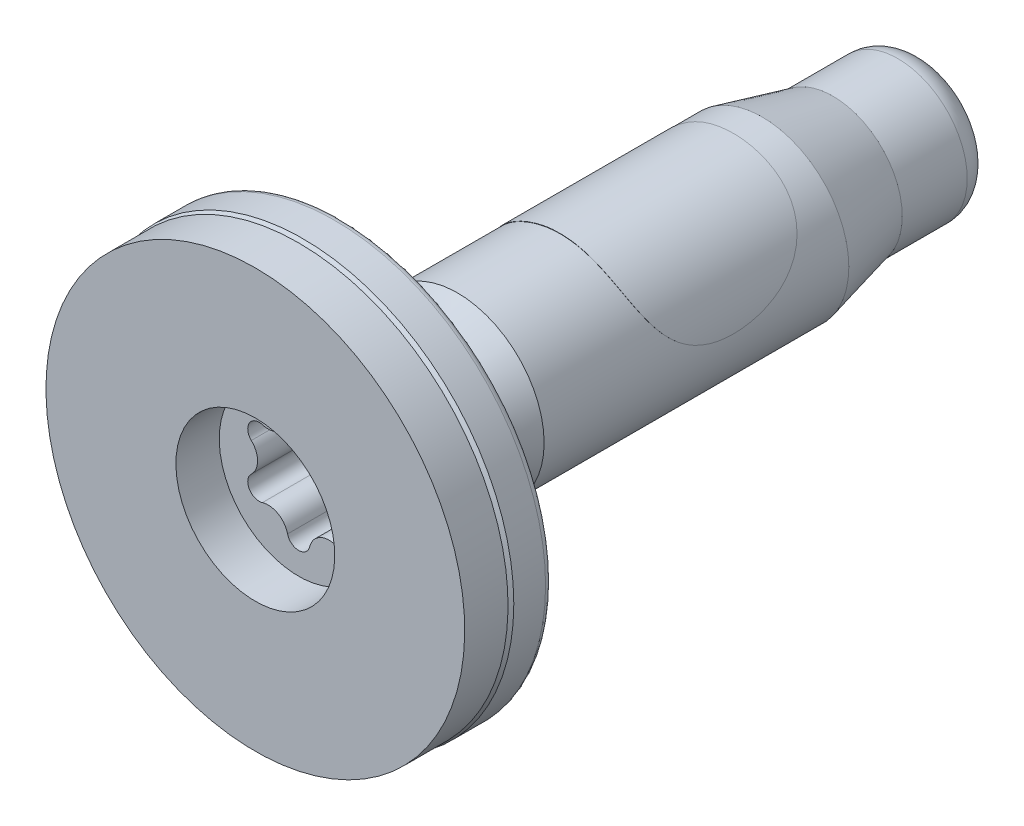
SolidWorks part; units mm, degrees
material "Plain Carbon Steel"
ref_plane "Front Plane" through (0, 0, 0) normal (0, 0, 1) x (1, 0, 0)
ref_plane "Top Plane" through (0, 0, 0) normal (0, 1, 0) x (1, 0, 0)
ref_plane "Right Plane" through (0, 0, 0) normal (1, 0, 0) x (0, 0, -1)
sketch "head-sketch" plane through (0, 0, 0) normal (1, 0, 0) x (0, 0, -1)
  line L0 (0, 0) -> (-4.4, 0) construction
  line L1 (0, 0) -> (0, 5)
  line L2 (0, 5) -> (-4.15, 5)
  line L3 (-4.4, 2.8) -> (-4.4, 0) construction
  line L4 (-4.4, 2.8) -> (-4.1899, 2.016)
  line L5 (-4.1899, 2.016) -> (-4.1899, 0)
  line L6 (-4.1899, 0) -> (0, 0)
  line L7 (-4.4, 2.8) -> (-4.4, 4.75)
  arc A1 (-4.4, 4.75) -> (-4.15, 5) centre (-4.15, 4.75) cw
  dimension "r" = 0.25
  dimension "dk" = 10
  dimension "D2" = 15
  dimension "k" = 4.4
  dimension "A-ref" = 5.6
  dimension "B-ref" = 4.032
ref_plane "6-lobe-plane" through (0, 0, 4.4) normal (0, 0, 1) x (1, 0, 0)
sketch "6-lobe-sketch" plane through (0, 0, 4.4) normal (0, 0, 1) x (1, 0, 0)
  line L0 (0, 0) -> (0, 2.8) construction
  line L1 (0, 0) -> (1.008, 1.7459) construction
  line L2 (1.008, 1.7459) -> (1.498, 2.5946) construction
  line L3 (0, 0) -> (2.4249, 1.4) construction
  line L4 (0, 0) -> (2.4249, -1.4) construction
  line L5 (0, 0) -> (2.996, 0) construction
  line L6 (0, 0) -> (0, -2.8) construction
  line L7 (0, 0) -> (1.498, -2.5946) construction
  line L8 (0, 0) -> (-2.996, 0) construction
  line L9 (0, 0) -> (-1.498, 2.5946) construction
  line L10 (0, 0) -> (-1.498, -2.5946) construction
  line L11 (0, 0) -> (-2.4249, -1.4) construction
  line L12 (0, 0) -> (-2.4249, 1.4) construction
  arc A17 (0.5442, 2.3693) -> (-0.5442, 2.3693) centre (0, 2.2408) ccw
  arc A18 (0.5442, 2.3693) -> (1.7798, 1.656) centre (1.498, 2.5946) ccw
  arc A19 (2.324, 0.7133) -> (1.7798, 1.656) centre (1.9406, 1.1204) ccw
  arc A20 (2.324, 0.7133) -> (2.324, -0.7133) centre (2.996, 0) ccw
  arc A21 (-0.5442, -2.3693) -> (0.5442, -2.3693) centre (0, -2.2408) ccw
  arc A22 (1.7798, -1.656) -> (2.324, -0.7133) centre (1.9406, -1.1204) ccw
  arc A23 (1.7798, -1.656) -> (0.5442, -2.3693) centre (1.498, -2.5946) ccw
  arc A24 (-1.7798, 1.656) -> (-2.324, 0.7133) centre (-1.9406, 1.1204) ccw
  arc A25 (-2.324, -0.7133) -> (-1.7798, -1.656) centre (-1.9406, -1.1204) ccw
  arc A26 (-0.5442, -2.3693) -> (-1.7798, -1.656) centre (-1.498, -2.5946) ccw
  arc A27 (-2.324, -0.7133) -> (-2.324, 0.7133) centre (-2.996, 0) ccw
  arc A28 (-1.7798, 1.656) -> (-0.5442, 2.3693) centre (-1.498, 2.5946) ccw
  arc A29 (-0.5442, 2.3693) -> (-1.7798, 1.656) centre (-1.498, 2.5946) ccw construction
  arc A30 (-1.4563, 0.8408) -> (-1.7798, 1.656) centre (-1.9406, 1.1204) ccw construction
  arc A31 (-2.324, 0.7133) -> (-1.4563, 0.8408) centre (-1.9406, 1.1204) ccw construction
  arc A32 (-2.324, 0.7133) -> (-2.324, -0.7133) centre (-2.996, 0) ccw construction
  arc A33 (-1.4563, -0.8408) -> (-2.324, -0.7133) centre (-1.9406, -1.1204) ccw construction
  arc A34 (-1.7798, -1.656) -> (-1.4563, -0.8408) centre (-1.9406, -1.1204) ccw construction
  arc A35 (-1.7798, -1.656) -> (-0.5442, -2.3693) centre (-1.498, -2.5946) ccw construction
  arc A36 (0, -1.6816) -> (-0.5442, -2.3693) centre (0, -2.2408) ccw construction
  arc A37 (0.5442, -2.3693) -> (0, -1.6816) centre (0, -2.2408) ccw construction
  arc A38 (0.5442, -2.3693) -> (1.7798, -1.656) centre (1.498, -2.5946) ccw construction
  arc A39 (1.4563, -0.8408) -> (1.7798, -1.656) centre (1.9406, -1.1204) ccw construction
  arc A40 (2.324, -0.7133) -> (1.4563, -0.8408) centre (1.9406, -1.1204) ccw construction
  arc A41 (2.324, -0.7133) -> (2.324, 0.7133) centre (2.996, 0) ccw construction
  arc A42 (1.4563, 0.8408) -> (2.324, 0.7133) centre (1.9406, 1.1204) ccw construction
  arc A43 (1.7798, 1.656) -> (1.4563, 0.8408) centre (1.9406, 1.1204) ccw construction
  arc A44 (1.7798, 1.656) -> (0.5442, 2.3693) centre (1.498, 2.5946) ccw construction
  arc A45 (0, 1.6816) -> (0.5442, 2.3693) centre (0, 2.2408) ccw construction
  arc A46 (-0.5442, 2.3693) -> (0, 1.6816) centre (0, 2.2408) ccw construction
  circle A47 centre (0, 0) radius 2.8 construction
  circle A48 centre (0, 0) radius 2.016 construction
  dimension "D1" = 60
  dimension "C-6-lobe" = 1.96
  dimension "A-6-lobe" = 5.6
  dimension "B-6-lobe" = 4.032
sketch "dia-sketch" plane through (0, 0, 0) normal (0, 0, 1) x (1, 0, 0)
  circle A0 centre (0, 0) radius 3
  dimension "dia" = 6
sketch "length-sketch" plane through (0, 0, 0) normal (1, 0, 0) x (0, 0, -1)
  line L0 (0, 0) -> (17, 0) construction
  dimension "length" = 17
ref_plane "length-end-plane" through (0, 0, -17) normal (0, 0, -1) x (-1, 0, 0)
sketch "pitch-sketch" [suppressed] plane through (0, 0, 0) normal (1, 0, 0) x (0, 0, -1)
  line L0 (0, 0) -> (0.4, 0)
  dimension "pitch" = 1
sketch "thread-sketch" plane through (0, 0, 0) normal (1, 0, 0) x (0, 0, -1)
  line L0 (0, 0) -> (17, 0) construction
  line L1 (0, 0) -> (17, 0) construction
  line L2 (0, 3) -> (4, 3)
  line L3 (4, 3) -> (3, 2.675)
  line L4 (3, 2.675) -> (0, 2.675)
  line L5 (0, 2.675) -> (0, 3)
  line L6 (0, 2.675) -> (0, 0) construction
  dimension "Dia-2" = 6
  dimension "threadtransition" = 1
  dimension "pitch-dia" = 5.35
  dimension "runout" = 4
sketch "chamfer-sketch" plane through (0, 0, 0) normal (1, 0, 0) x (0, 0, -1)
  line L0 (17, 0) -> (17, 2.4) construction
  line L2 (0, 0) -> (17, 0) construction
  line L3 (0, 0) -> (17, 0) construction
  line L4 (17, 2.4) -> (17, 3)
  line L5 (17, 3) -> (16.2849, 3)
  line L6 (16.2849, 3) -> (17, 2.4)
  dimension "minor-dia" = 4.8
  dimension "D1" = 50
  dimension "dia-3" = 6
sketch "fillet-sketch" plane through (0, 0, 0) normal (1, 0, 0) x (0, 0, -1)
  line L0 (0, 0) -> (17, 0) construction
  line L1 (0, 0) -> (17, 0) construction
  line L2 (0, 2.675) -> (1, 2.675)
  line L3 (0, 2.675) -> (0, 3.4)
  line L4 (0, 2.675) -> (0, 0) construction
  line L5 (0.1464, 3.0375) -> (0, 3.0375) construction
  arc A0 (1, 2.675) -> (0.1464, 3.0375) centre (1, 3.8613) cw
  arc A1 (0, 3.4) -> (0.1464, 3.0375) centre (0.522, 3.4) ccw
  dimension "r" = 0.522
  dimension "pitch-fillet" = 1
  dimension "fillet-dia" = 5.35
  dimension "da" = 6.8
sketch "socket-depth-sketch" plane through (0, 0, 0) normal (1, 0, 0) x (0, 0, -1)
  line L0 (-4.4, 0) -> (-2.11, 0) construction
  line L1 (-4.1899, 0) -> (0, 0) construction
  line L2 (-2.11, 0) -> (-0.86, 0) construction
  dimension "t" = 2.29
  dimension "t+" = 1.25
ref_plane "socket-bottom-plane" through (0, 0, 0.86) normal (0, 0, -1) x (-1, 0, 0)
sketch "socket-revolve-sketch" plane through (0, 0, 0) normal (1, 0, 0) x (0, 0, -1)
  line L0 (0, 0) -> (0, 5)
  line L1 (0, 5) -> (-2.11, 5)
  line L2 (0, 5) -> (-4.15, 5) construction
  line L3 (-2.11, 5) -> (-2.11, 2.8)
  line L4 (-2.11, 2.8) -> (-0.86, 0)
  line L5 (-0.86, 0) -> (0, 0)
  line L6 (0, 0) -> (1.1467, 0) construction
  line L7 (-2.11, 2.8) -> (-2.11, 0) construction
  line L8 (-2.11, 2.8) -> (-4.4, 2.8) construction
sketch "mat-dia-sketch" plane through (0, 0, -17) normal (0, 0, -1) x (-1, 0, 0)
  circle A0 centre (0, 0) radius 2.4
  dimension "Dx" = 4.8
sketch "mat-length-sketch" plane through (0, 0, 0) normal (1, 0, 0) x (0, 0, -1)
  line L0 (17, 0) -> (20, 0) construction
  dimension "Z4" = 3
ref_plane "mat-end-plane" through (0, 0, -20) normal (0, 0, -1) x (-1, 0, 0)
sketch "mat-cut" plane through (0, 0, 0) normal (1, 0, 0) x (0, 0, -1)
  line L0 (17, 2.4) -> (17, 3)
  line L1 (17, 3) -> (14.55, 3)
  line L2 (14.55, 3) -> (17, 2.4)
  line L3 (19.25, 2.4) -> (20, 2.4)
  line L4 (20, 2.4) -> (20, 2)
  line L5 (17, 0) -> (17, 2.4) construction
  line L7 (17, 0) -> (20, 0) construction
  line L8 (17, -2.4) -> (17, 2.4) construction
  line L9 (17, 2.4) -> (19.25, 2.4) construction
  line L10 (20, -0.8397) -> (20, 0.8397) construction
  line L11 (20, 2) -> (20, 0) construction
  arc A0 (19.25, 2.4) -> (20, 2) centre (19.25, 1.4969) cw
  dimension "mat-dia" = 6
  dimension "U-ref" = 2.45
  dimension "Z5" = 0.75
  dimension "Dy" = 4
sketch "VSMP-boss" plane through (0, 0, 0) normal (1, 0, 0) x (0, 0, -1)
  line L0 (17, 0) -> (12.1951, 0) construction
  line L1 (17, 0) -> (17.9, 0)
  line L2 (17.9, 0) -> (17.9, 2.15)
  line L3 (17.9, 2.15) -> (17, 2.4)
  line L4 (17, 2.4) -> (17, 0)
  dimension "Z4" = 0.9
  dimension "Dt" = 4.3
sketch "VSMP-cut" plane through (0, 0, 0) normal (1, 0, 0) x (0, 0, -1)
  line L0 (17, 0) -> (12.1951, 0) construction
  line L1 (17, 2.4) -> (17, 3)
  line L2 (17, 3) -> (14.45, 3)
  line L3 (14.45, 3) -> (17, 2.4)
  dimension "Uref" = 2.55
sketch "SDpoint" plane through (0, 0, 0) normal (1, 0, 0) x (0, 0, -1)
  line L0 (17, 0) -> (9.1343, 0) construction
  line L2 (17, 0) -> (18.5, 0)
  line L3 (18.5, 0) -> (18.5, 2)
  line L4 (18.5, 2) -> (17.4, 2)
  line L5 (17.4, 2) -> (17, 2.4)
  line L6 (17, 2.4) -> (17, 0)
  dimension "D1" = 45
  dimension "z1" = 1.5
  dimension "dp" = 4
sketch "LDpoint" plane through (0, 0, 0) normal (1, 0, 0) x (0, 0, -1)
  line L0 (17, 0) -> (9.1777, 0) construction
  line L2 (17, 0) -> (20, 0)
  line L3 (20, 0) -> (20, 2)
  line L4 (20, 2) -> (17.4, 2)
  line L5 (17.4, 2) -> (17, 2.4)
  line L6 (17, 2.4) -> (17, 0)
  dimension "D1" = 45
  dimension "dp" = 4
  dimension "z2" = 3
sketch "PCpoint" plane through (0, 0, 0) normal (1, 0, 0) x (0, 0, -1)
  line L0 (17, 0) -> (12.2128, 0) construction
  line L1 (17, 0) -> (20, 0)
  line L2 (20, 0) -> (20, 0.25)
  line L3 (20, 0.25) -> (18, 2.25)
  line L4 (18, 2.25) -> (17.3369, 2.25)
  line L5 (17, 0) -> (17, 2.4) construction
  line L6 (17, 2.4) -> (17.3369, 2.25)
  line L7 (17, 2.4) -> (15.7133, 3)
  line L8 (15.7133, 3) -> (15.7133, 0)
  line L10 (15.7133, 0) -> (17, 0)
  line L11 (15.7133, 3) -> (17, 3) construction
  dimension "D1" = 25
  dimension "D2" = 24
  dimension "D3" = 45
  dimension "z4" = 3
  dimension "z5" = 2
  dimension "D4" = 1.2867
  dimension "dx" = 4.5
sketch "PCpoint-cut" plane through (0, 0, 0) normal (1, 0, 0) x (0, 0, -1)
  line L5 (17, 2.4) -> (15.7133, 3) construction
  line L6 (17, 2.4) -> (15.7133, 3)
  line L7 (15.7133, 3) -> (17, 3)
  line L8 (17, 3) -> (17, 2.4)
  line L9 (17, 0) -> (15.7133, 0) construction
  dimension "cutlength" = 1.2867
sketch "flat-washer" plane through (0, 0, 0) normal (1, 0, 0) x (0, 0, -1)
  line L0 (0, 0) -> (0, 2.81) construction
  line L1 (0, 0) -> (0, 5) construction
  line L2 (0, 0) -> (0.25, 0) construction
  line L3 (0, 2.81) -> (0.25, 2.81)
  line L4 (0, 2.81) -> (0, 2.5)
  line L5 (0, 2.5) -> (0.25, 2.5)
  line L6 (0.25, 2.81) -> (0.25, 2.5)
  line L7 (0, 0) -> (17, 0) construction
  line L8 (0.25, 0) -> (0.25, 2.81) construction
  dimension "D1" = 0.25
  dimension "D2" = 5
  dimension "ID" = 5.62
sketch "conical-washer" plane through (0, 0, 0) normal (1, 0, 0) x (0, 0, -1)
  line L0 (0, 0) -> (0, 2.81) construction
  line L1 (0, 0) -> (0, 5) construction
  line L2 (0, 2.81) -> (0.5, 2.81) construction
  line L3 (0.5, 2.81) -> (0.5, 2) construction
  line L4 (0.5, 2) -> (0, 2) construction
  line L5 (0, 2) -> (0, 2.81) construction
  line L6 (0.5, 2.81) -> (0.5, 0) construction
  line L7 (0, 0) -> (17, 0) construction
  line L8 (0.5, 0) -> (0, 0) construction
  line L9 (0, 2.81) -> (0.25, 2.81) construction
  line L10 (0, 2.724) -> (0.2347, 2.81)
  line L11 (0.2347, 2.81) -> (0.5, 2.086)
  line L12 (0.5, 2.086) -> (0.2653, 2)
  line L13 (0.2653, 2) -> (0, 2.724)
  dimension "D1" = 0.5
  dimension "D2" = 4
  dimension "D3" = 0.25
sketch "double-washer" plane through (0, 0, 0) normal (1, 0, 0) x (0, 0, -1)
  line L0 (0.2653, 2) -> (0, 2.724) construction
  line L1 (0, 2.724) -> (0.2347, 2.81) construction
  line L2 (0.2347, 2.81) -> (0.5, 2.086) construction
  line L3 (0.5, 2.086) -> (0.2653, 2) construction
  line L4 (0.2653, 2) -> (0, 2.724)
  line L5 (0, 2.724) -> (0.2347, 2.81)
  line L6 (0.2347, 2.81) -> (0.5, 2.086)
  line L7 (0.5, 2.086) -> (0.2653, 2)
  line L8 (0, 2.5) -> (0.25, 2.5) construction
  line L9 (0.5, 2.81) -> (0.75, 2.81)
  line L10 (0.5, 2.81) -> (0.5, 2.5)
  line L11 (0.5, 2.5) -> (0.75, 2.5)
  line L12 (0.75, 2.81) -> (0.75, 2.5)
  line L13 (0, 0) -> (0.75, 0) construction
  line L14 (0, 0) -> (17, 0) construction
  line L15 (0.75, 0) -> (0.75, 2.81) construction
sketch "B" plane through (0, 0, 0) normal (1, 0, 0) x (0, 0, -1)
  line L0 (17, 0) -> (-21, 0) construction
  line L1 (0, 0) -> (17, 0) construction
  dimension "B" = 38
sketch "hA" plane through (0, 0, 0) normal (1, 0, 0) x (0, 0, -1)
  line L0 (0, 0) -> (0.75, 0) construction
  line L1 (0, 0) -> (17, 0) construction
  dimension "hA" = 0.75
sketch "flat-thread-cut" plane through (0, 0, 0) normal (1, 0, 0) x (0, 0, -1)
  line L0 (0, 3) -> (0, 0) construction
  line L1 (0, 0) -> (0, 5) construction
  line L2 (0, 0) -> (0.25, 0) construction
  line L3 (0, 0) -> (17, 0) construction
  line L4 (0.25, 0) -> (0.25, 2.675) construction
  line L5 (0.25, 2.675) -> (1.25, 3)
  line L6 (1.25, 3) -> (0, 3)
  line L7 (0, 3) -> (0, 2.675)
  line L8 (0, 2.675) -> (0.25, 2.675)
  dimension "D1" = 1
  dimension "D2" = 6
  dimension "A" = 0.25
  dimension "D4" = 5.35
sketch "conical-thread-cut" plane through (0, 0, 0) normal (1, 0, 0) x (0, 0, -1)
  line L0 (0, 3) -> (0, 0) construction
  line L2 (0, 0) -> (0.5, 0) construction
  line L4 (0.5, 0) -> (0.5, 2.675) construction
  line L5 (0.5, 2.675) -> (1.5, 3)
  line L6 (1.5, 3) -> (0, 3)
  line L7 (0, 3) -> (0, 2.675)
  line L8 (0, 2.675) -> (0.5, 2.675)
  dimension "D1" = 1
  dimension "D2" = 6
  dimension "D4" = 5.35
  dimension "A" = 0.5
sketch "double-thread-cut" plane through (0, 0, 0) normal (1, 0, 0) x (0, 0, -1)
  line L0 (0, 3) -> (0, 0) construction
  line L2 (0, 0) -> (0.75, 0) construction
  line L4 (0.75, 0) -> (0.75, 2.675) construction
  line L5 (0.75, 2.675) -> (1.75, 3)
  line L6 (1.75, 3) -> (0, 3)
  line L7 (0, 3) -> (0, 2.675)
  line L8 (0, 2.675) -> (0.75, 2.675)
  dimension "D1" = 1
  dimension "D2" = 6
  dimension "D4" = 5.35
  dimension "A" = 0.75
sketch "head-cut" plane through (0, 0, 4.4) normal (0, 0, 1) x (1, 0, 0)
  circle A0 centre (0, 0) radius 5.5
  dimension "OD" = 11
ref_plane "head-cut-end" through (0, 0, 0) normal (0, 0, -1) x (-1, 0, 0)
sketch "low-head" plane through (0, 0, 0) normal (1, 0, 0) x (0, 0, -1)
  line L0 (0, 0) -> (3.5646, 0) construction
  line L1 (0, 0) -> (-1.5, 0)
  line L2 (-1.5, 0) -> (-1.5, 7.15)
  line L3 (-1.5, 7.15) -> (-1.35, 7.3)
  line L4 (-1.35, 7.3) -> (-0.25, 7.3)
  line L5 (0, 7.05) -> (0, 0)
  arc A0 (-0.25, 7.3) -> (0, 7.05) centre (-0.25, 7.05) cw
  dimension "r-low" = 0.25
  dimension "k-low" = 1.5
  dimension "d2" = 14.6
  dimension "v" = 0.15
  dimension "D3" = 45
sketch "low-socket-depth" plane through (0, 0, 0) normal (1, 0, 0) x (0, 0, -1)
  line L0 (-1.5, 0) -> (0.6, 0) construction
  line L1 (0, 0) -> (-1.5, 0) construction
  line L2 (0.6, 0) -> (1.05, 0) construction
  line L3 (0, 0) -> (3.5646, 0) construction
  dimension "t" = 2.1
  dimension "t+" = 0.45
ref_plane "low-6-lobe" through (0, 0, 1.5) normal (0, 0, 1) x (1, 0, 0)
ref_plane "low-socket-end" through (0, 0, -1.05) normal (0, 0, -1) x (-1, 0, 0)
sketch "small-6-lobe" plane through (0, 0, 1.5) normal (0, 0, 1) x (1, 0, 0)
  line L0 (0, 1.5805) -> (0, -1.5805) construction
  line L1 (1.0566, 1.8301) -> (0, 0) construction
  circle A15 centre (0, 0) radius 1.422 construction
  circle A16 centre (0, 0) radius 1.975 construction
  arc A17 (0.3839, 1.6712) -> (-0.3839, 1.6712) centre (0, 1.5805) ccw
  arc A18 (0.3839, 1.6712) -> (1.2554, 1.1681) centre (1.0566, 1.8301) ccw
  arc A19 (-0.3839, -1.6712) -> (0.3839, -1.6712) centre (0, -1.5805) ccw
  arc A20 (1.6393, 0.5032) -> (1.2554, 1.1681) centre (1.3688, 0.7903) ccw
  arc A21 (1.2554, -1.1681) -> (1.6393, -0.5032) centre (1.3688, -0.7903) ccw
  arc A22 (-1.6393, -0.5032) -> (-1.2554, -1.1681) centre (-1.3688, -0.7903) ccw
  arc A23 (-1.2554, 1.1681) -> (-1.6393, 0.5032) centre (-1.3688, 0.7903) ccw
  arc A24 (1.6393, 0.5032) -> (1.6393, -0.5032) centre (2.1132, 0) ccw
  arc A25 (1.2554, -1.1681) -> (0.3839, -1.6712) centre (1.0566, -1.8301) ccw
  arc A26 (-0.3839, -1.6712) -> (-1.2554, -1.1681) centre (-1.0566, -1.8301) ccw
  arc A27 (-1.6393, -0.5032) -> (-1.6393, 0.5032) centre (-2.1132, 0) ccw
  arc A28 (-1.2554, 1.1681) -> (-0.3839, 1.6712) centre (-1.0566, 1.8301) ccw
  arc A29 (1.4924, 1.2936) -> (0.374, 1.9393) centre (1.0566, 1.8301) ccw construction
  arc A30 (1.8665, -0.6457) -> (1.8665, 0.6457) centre (2.1132, 0) ccw construction
  arc A31 (0.374, -1.9393) -> (1.4924, -1.2936) centre (1.0566, -1.8301) ccw construction
  arc A32 (-1.4924, -1.2936) -> (-0.374, -1.9393) centre (-1.0566, -1.8301) ccw construction
  arc A33 (-1.8665, 0.6457) -> (-1.8665, -0.6457) centre (-2.1132, 0) ccw construction
  arc A34 (-0.374, 1.9393) -> (-1.4924, 1.2936) centre (-1.0566, 1.8301) ccw construction
  arc A35 (-0.3401, 1.3807) -> (0, 1.1861) centre (0, 1.5805) ccw construction
  arc A36 (0, 1.1861) -> (0.3401, 1.3807) centre (0, 1.5805) ccw construction
  arc A37 (1.0257, 0.9849) -> (1.3658, 0.3958) centre (1.3688, 0.7903) ccw construction
  arc A38 (1.3658, -0.3958) -> (1.0257, -0.9849) centre (1.3688, -0.7903) ccw construction
  arc A39 (0.3401, -1.3807) -> (0, -1.1861) centre (0, -1.5805) ccw construction
  arc A40 (0, -1.1861) -> (-0.3401, -1.3807) centre (0, -1.5805) ccw construction
  arc A41 (-1.0257, -0.9849) -> (-1.3658, -0.3958) centre (-1.3688, -0.7903) ccw construction
  arc A42 (-1.3658, 0.3958) -> (-1.0257, 0.9849) centre (-1.3688, 0.7903) ccw construction
  arc A43 (0.374, 1.9393) -> (0.3839, 1.6712) centre (1.0566, 1.8301) ccw construction
  arc A44 (1.2554, 1.1681) -> (1.4924, 1.2936) centre (1.0566, 1.8301) ccw construction
  arc A45 (1.8665, 0.6457) -> (1.6393, 0.5032) centre (2.1132, 0) ccw construction
  arc A46 (1.6393, -0.5032) -> (1.8665, -0.6457) centre (2.1132, 0) ccw construction
  arc A47 (1.4924, -1.2936) -> (1.2554, -1.1681) centre (1.0566, -1.8301) ccw construction
  arc A48 (0.3839, -1.6712) -> (0.374, -1.9393) centre (1.0566, -1.8301) ccw construction
  arc A49 (-0.374, -1.9393) -> (-0.3839, -1.6712) centre (-1.0566, -1.8301) ccw construction
  arc A50 (-1.2554, -1.1681) -> (-1.4924, -1.2936) centre (-1.0566, -1.8301) ccw construction
  arc A51 (-1.8665, -0.6457) -> (-1.6393, -0.5032) centre (-2.1132, 0) ccw construction
  arc A52 (-1.6393, 0.5032) -> (-1.8665, 0.6457) centre (-2.1132, 0) ccw construction
  arc A53 (-1.4924, 1.2936) -> (-1.2554, 1.1681) centre (-1.0566, 1.8301) ccw construction
  arc A54 (-0.3839, 1.6712) -> (-0.374, 1.9393) centre (-1.0566, 1.8301) ccw construction
  arc A55 (0.3401, 1.3807) -> (0.3839, 1.6712) centre (0, 1.5805) ccw construction
  arc A56 (1.2554, 1.1681) -> (1.0257, 0.9849) centre (1.3688, 0.7903) ccw construction
  arc A57 (1.3658, 0.3958) -> (1.6393, 0.5032) centre (1.3688, 0.7903) ccw construction
  arc A58 (1.6393, -0.5032) -> (1.3658, -0.3958) centre (1.3688, -0.7903) ccw construction
  arc A59 (1.0257, -0.9849) -> (1.2554, -1.1681) centre (1.3688, -0.7903) ccw construction
  arc A60 (0.3839, -1.6712) -> (0.3401, -1.3807) centre (0, -1.5805) ccw construction
  arc A61 (-0.3401, -1.3807) -> (-0.3839, -1.6712) centre (0, -1.5805) ccw construction
  arc A62 (-1.2554, -1.1681) -> (-1.0257, -0.9849) centre (-1.3688, -0.7903) ccw construction
  arc A63 (-1.3658, -0.3958) -> (-1.6393, -0.5032) centre (-1.3688, -0.7903) ccw construction
  arc A64 (-1.6393, 0.5032) -> (-1.3658, 0.3958) centre (-1.3688, 0.7903) ccw construction
  arc A65 (-1.0257, 0.9849) -> (-1.2554, 1.1681) centre (-1.3688, 0.7903) ccw construction
  arc A66 (-0.3839, 1.6712) -> (-0.3401, 1.3807) centre (0, 1.5805) ccw construction
  point P2 (0, 0)
  dimension "A" = 3.95
  dimension "B" = 2.844
  dimension "C" = 1.3825
  dimension "D3" = 30
sketch "low-socket-revolve" plane through (0, 0, 0) normal (1, 0, 0) x (0, 0, -1)
  line L0 (0.6, 1.975) -> (1.05, 0)
  line L1 (1.05, 0) -> (1.1, 0)
  line L2 (1.1, 0) -> (1.1, 2.075)
  line L3 (1.1, 2.075) -> (0.6, 2.075)
  line L4 (0.6, 2.075) -> (0.6, 1.975)
  line L5 (0.6, 1.975) -> (-1.5, 1.975) construction
  line L6 (1.05, -0.165) -> (1.05, 0.165) construction
  line L7 (0.6, 1.975) -> (0.6, 0) construction
  line L8 (1.05, 0) -> (0.6, 0) construction
  line L9 (-1.5, 0) -> (-1.5, 7.15) construction
  dimension "D1" = 0.1
  dimension "D2" = 0.05
  dimension "A" = 3.95
sketch "threads" plane through (0, 0, 0) normal (1, 0, 0) x (0, 0, -1)
  line L0 (0, 0) -> (17, 0) construction
  line L1 (0, 0) -> (17, 0) construction
  line L2 (17, 2.4) -> (4, 2.4)
  line L3 (17, 2.4) -> (17, 3)
  line L4 (17, 3) -> (16.2849, 3)
  line L5 (16.2849, 3) -> (17, 2.4)
  line L8 (16.2849, 3) -> (17, 2.4) construction
  line L9 (4, 2.4) -> (3, 2.675)
  line L10 (4, 3) -> (0, 3)
  line L11 (3, 2.675) -> (4, 3)
  line L12 (0, 2.675) -> (3, 2.675)
  line L13 (0, 3) -> (0, 2.675)
  line L15 (3, 2.675) -> (4, 3) construction
  line L18 (17, -2.4) -> (4, -2.4)
  line L19 (4, -2.4) -> (3, -2.675)
  dimension "D1" = 0
  dimension "D2" = 0
sketch "patches-1" plane through (0, 0, 0) normal (0, 1, 0) x (1, 0, 0)
  line L0 (0, 17) -> (0, 14.55)
  dimension "plane length" = 2.45
ref_plane "patches-2" through (0, 0, -14.55) normal (0, 0, -1) x (-1, 0, 0)
sketch "180-patch-1" plane through (0, 0, 0) normal (1, 0, 0) x (0, 0, -1)
  line L0 (0, 0) -> (17, 0) construction
  line L1 (7.55, 3) -> (7.55, 0) construction
  line L2 (7.55, 0) -> (10.55, 0) construction
  circle A0 centre (10.55, 3) radius 3
  dimension "D2" = 4
  dimension "D1" = 6
sketch "180-patch-2" plane through (0, 0, 0) normal (0, 1, 0) x (1, 0, 0)
  line L0 (0, 10.55) -> (4.5, 10.55) construction
  line L1 (0, 0) -> (0, 10.55) construction
  line L2 (0, 10.55) -> (-4.5, 10.55) construction
  dimension "D1" = 9
ref_plane "180-patch-3" through (4.5, 0, -10.55) normal (1, 0, 0) x (0, 0, -1)
sketch "180-patch-4" plane through (0, 0, -17) normal (0, 0, -1) x (-1, 0, 0)
  circle A0 centre (0, 0) radius 3.01
  circle A1 centre (0, 0) radius 9
  dimension "D1" = 6.02
  dimension "D2" = 18
ref_plane "180-patch-5" through (0, 0, -7.55) normal (0, 0, -1) x (-1, 0, 0)
ref_plane "180-patch-6" through (-4.5, 0, -10.55) normal (-1, 0, 0) x (0, 0, 1)
sketch "360-patch" plane through (0, 0, 0) normal (1, 0, 0) x (0, 0, -1)
  line L0 (0, 0) -> (17, 0) construction
  line L1 (7.55, 3) -> (13.55, 3)
  line L2 (7.55, 3) -> (7.55, 3.01)
  line L3 (7.55, 3.01) -> (13.55, 3.01)
  line L4 (13.55, 3) -> (13.55, 3.01)
  line L6 (14.55, 0) -> (14.55, 3) construction
  line L7 (14.55, -1.0038) -> (14.55, 1.0038) construction
  line L8 (13.55, 3) -> (14.55, 3) construction
  dimension "D1" = 6
  dimension "D3" = 6
  dimension "D4" = 0.01
  dimension "D2" = 1
sketch "Sketch8" plane through (0, 0, 0) normal (1, 0, 0) x (0, 0, -1)
  line L0 (0, 0) -> (-4.4, 0) construction
  line L1 (-4.4, 2.8) -> (-4.1899, 2.016) construction
  line L2 (-4.1899, 2.016) -> (-4.1899, 0) construction
  line L3 (-4.1899, 0) -> (0, 0) construction
  line L4 (0, 0) -> (0, 5) construction
  line L5 (0, 5) -> (-4.15, 5) construction
  line L6 (0, 0) -> (-4.4, 0) construction
  line L7 (-4.4, 2.8) -> (-4.1899, 2.016)
  line L8 (-4.1899, 2.016) -> (-4.1899, 0)
  line L9 (-4.1899, 0) -> (0, 0)
  line L10 (0, 0) -> (0, 5)
  line L11 (0, 5) -> (-4.15, 5)
  line L12 (-4.4, 2.8) -> (-4.4, 4.75) construction
  line L13 (-4.4, 2.8) -> (-4.4, 4.75)
  arc A1 (-4.15, 5) -> (-4.4, 4.75) centre (-4.15, 4.75) ccw construction
  arc A2 (-4.15, 5) -> (-4.4, 4.75) centre (-4.15, 4.75) ccw
revolve "Head-Revolve1" add sketch "Sketch8" angle 360 about L6 region at (0, 2.5287, 2.1492)
sketch "Sketch9" plane through (0, 0, 4.4) normal (0, 0, 1) x (1, 0, 0)
  arc A36 (0.5442, 2.3693) -> (1.7798, 1.656) centre (1.498, 2.5946) ccw
  arc A37 (2.324, 0.7133) -> (1.7798, 1.656) centre (1.9406, 1.1204) ccw
  arc A38 (2.324, 0.7133) -> (2.324, -0.7133) centre (2.996, 0) ccw
  arc A39 (1.7798, -1.656) -> (2.324, -0.7133) centre (1.9406, -1.1204) ccw
  arc A40 (1.7798, -1.656) -> (0.5442, -2.3693) centre (1.498, -2.5946) ccw
  arc A41 (-0.5442, -2.3693) -> (0.5442, -2.3693) centre (0, -2.2408) ccw
  arc A42 (-0.5442, -2.3693) -> (-1.7798, -1.656) centre (-1.498, -2.5946) ccw
  arc A43 (-2.324, -0.7133) -> (-1.7798, -1.656) centre (-1.9406, -1.1204) ccw
  arc A44 (-2.324, -0.7133) -> (-2.324, 0.7133) centre (-2.996, 0) ccw
  arc A45 (-1.7798, 1.656) -> (-2.324, 0.7133) centre (-1.9406, 1.1204) ccw
  arc A46 (-1.7798, 1.656) -> (-0.5442, 2.3693) centre (-1.498, 2.5946) ccw
  arc A47 (0.5442, 2.3693) -> (-0.5442, 2.3693) centre (0, 2.2408) ccw
  arc A48 (0.5442, 2.3693) -> (1.7798, 1.656) centre (1.498, 2.5946) ccw
  arc A49 (2.324, 0.7133) -> (1.7798, 1.656) centre (1.9406, 1.1204) ccw
  arc A50 (2.324, 0.7133) -> (2.324, -0.7133) centre (2.996, 0) ccw
  arc A51 (1.7798, -1.656) -> (2.324, -0.7133) centre (1.9406, -1.1204) ccw
  arc A52 (1.7798, -1.656) -> (0.5442, -2.3693) centre (1.498, -2.5946) ccw
  arc A53 (-0.5442, -2.3693) -> (0.5442, -2.3693) centre (0, -2.2408) ccw
  arc A54 (-0.5442, -2.3693) -> (-1.7798, -1.656) centre (-1.498, -2.5946) ccw
  arc A55 (-2.324, -0.7133) -> (-1.7798, -1.656) centre (-1.9406, -1.1204) ccw
  arc A56 (-2.324, -0.7133) -> (-2.324, 0.7133) centre (-2.996, 0) ccw
  arc A57 (-1.7798, 1.656) -> (-2.324, 0.7133) centre (-1.9406, 1.1204) ccw
  arc A58 (-1.7798, 1.656) -> (-0.5442, 2.3693) centre (-1.498, 2.5946) ccw
  arc A59 (0.5442, 2.3693) -> (-0.5442, 2.3693) centre (0, 2.2408) ccw
  dimension "D1" = 0
extrude "socket-Cut-Extrude1" cut sketch "Sketch9" against normal up to surface (3.54 mm away) up to plane "socket-bottom-plane"
sketch "Sketch12" plane through (0, 0, 0) normal (1, 0, 0) x (0, 0, -1)
  line L0 (-2.11, 5) -> (-2.11, 2.8) construction
  line L1 (-2.11, 2.8) -> (-0.86, 0) construction
  line L2 (-0.86, 0) -> (0, 0) construction
  line L3 (0, 0) -> (0, 5) construction
  line L4 (0, 5) -> (-2.11, 5) construction
  line L5 (-2.11, 5) -> (-2.11, 2.8)
  line L6 (-2.11, 2.8) -> (-0.86, 0)
  line L7 (-0.86, 0) -> (0, 0)
  line L8 (0, 0) -> (0, 5)
  line L9 (0, 5) -> (-2.11, 5)
  line L10 (0, 0) -> (1.1467, 0) construction
  line L11 (0, 0) -> (1.1467, 0) construction
revolve "Socket-Revolve2" add sketch "Sketch12" angle 360 about L11
sketch "Sketch13" plane through (0, 0, 0) normal (0, 0, 1) x (1, 0, 0)
  circle A0 centre (0, 0) radius 3 construction
  circle A1 centre (0, 0) radius 3
extrude "Length-Boss-Extrude1" add sketch "Sketch13" against normal up to surface (17 mm away) up to plane "length-end-plane"
sketch "Sketch14" plane through (0, 0, 0) normal (1, 0, 0) x (0, 0, -1)
  line L0 (0, 0) -> (17, 0) construction
  line L1 (0, 3) -> (4, 3) construction
  line L2 (4, 3) -> (3, 2.675) construction
  line L3 (3, 2.675) -> (0, 2.675) construction
  line L4 (0, 2.675) -> (0, 3) construction
  line L5 (0, 0) -> (17, 0) construction
  line L6 (0, 3) -> (4, 3)
  line L7 (4, 3) -> (3, 2.675)
  line L8 (3, 2.675) -> (0, 2.675)
  line L9 (0, 2.675) -> (0, 3)
revolve "Runout-Cut-Revolve1" cut sketch "Sketch14" angle 360 about L5
sketch "Sketch15" plane through (0, 0, 0) normal (1, 0, 0) x (0, 0, -1)
  line L0 (0, 2.675) -> (1, 2.675) construction
  line L1 (0, 2.675) -> (0, 3.4) construction
  line L2 (0, 0) -> (17, 0) construction
  line L3 (0, 2.675) -> (0, 0) construction
  line L4 (0, 2.675) -> (1, 2.675)
  line L5 (0, 2.675) -> (0, 3.4)
  line L6 (0, 0) -> (17, 0) construction
  line L7 (0, 2.675) -> (0, 0)
  arc A0 (0, 3.4) -> (0.1464, 3.0375) centre (0.522, 3.4) ccw construction
  arc A1 (0.1464, 3.0375) -> (1, 2.675) centre (1, 3.8613) ccw construction
  arc A2 (0, 3.4) -> (0.1464, 3.0375) centre (0.522, 3.4) ccw
  arc A3 (0.1464, 3.0375) -> (1, 2.675) centre (1, 3.8613) ccw
revolve "Fillet-Revolve3" add sketch "Sketch15" angle 360 about L6 region at (0, 2.8391, -0.2321)
sketch "Sketch16" plane through (0, 0, 0) normal (1, 0, 0) x (0, 0, -1)
  line L0 (0, 0) -> (17, 0) construction
  line L1 (17, 3) -> (16.2849, 3) construction
  line L2 (16.2849, 3) -> (17, 2.4) construction
  line L3 (17, 2.4) -> (17, 3) construction
  line L4 (0, 0) -> (17, 0) construction
  line L5 (17, 3) -> (16.2849, 3)
  line L6 (16.2849, 3) -> (17, 2.4)
  line L7 (17, 2.4) -> (17, 3)
revolve "Chamfer-Cut-Revolve2" cut sketch "Sketch16" angle 360 about L4
sketch "Sketch21" plane through (0, 0, -17) normal (0, 0, -1) x (-1, 0, 0)
  circle A0 centre (0, 0) radius 2.4 construction
  circle A1 centre (0, 0) radius 2.4
extrude "matpoint-Boss-Extrude1" add sketch "Sketch21" along normal up to surface (3 mm away) up to plane "mat-end-plane"
sketch "Sketch22" plane through (0, 0, 0) normal (1, 0, 0) x (0, 0, -1)
  line L0 (17, 0) -> (20, 0) construction
  line L1 (20, 2.4) -> (20, 2) construction
  line L2 (19.25, 2.4) -> (20, 2.4) construction
  line L3 (17, 3) -> (14.55, 3) construction
  line L4 (14.55, 3) -> (17, 2.4) construction
  line L5 (17, 2.4) -> (17, 3) construction
  line L6 (17, 0) -> (20, 0) construction
  line L7 (20, 2.4) -> (20, 2)
  line L8 (19.25, 2.4) -> (20, 2.4)
  line L9 (17, 3) -> (14.55, 3)
  line L10 (14.55, 3) -> (17, 2.4)
  line L11 (17, 2.4) -> (17, 3)
  arc A0 (20, 2) -> (19.25, 2.4) centre (19.25, 1.4969) ccw construction
  arc A1 (20, 2) -> (19.25, 2.4) centre (19.25, 1.4969) ccw
revolve "matpoint-Cut-Revolve1" cut sketch "Sketch22" angle 360 about L6
sketch "Sketch40" plane through (0, 0, 0) normal (1, 0, 0) x (0, 0, -1)
  line L0 (17, 0) -> (12.1951, 0) construction
  line L1 (17.9, 2.15) -> (17, 2.4) construction
  line L2 (17, 2.4) -> (17, 0) construction
  line L3 (17, 0) -> (17.9, 0) construction
  line L4 (17.9, 0) -> (17.9, 2.15) construction
  line L5 (17, 0) -> (12.1951, 0) construction
  line L6 (17.9, 2.15) -> (17, 2.4)
  line L7 (17, 2.4) -> (17, 0)
  line L8 (17, 0) -> (17.9, 0)
  line L9 (17.9, 0) -> (17.9, 2.15)
revolve "VSMP-revolve" [suppressed] add sketch "Sketch40" angle 360 about L5
sketch "Sketch41" plane through (0, 0, 0) normal (1, 0, 0) x (0, 0, -1)
  line L0 (17, 0) -> (12.1951, 0) construction
  line L1 (17, 3) -> (14.45, 3) construction
  line L2 (14.45, 3) -> (17, 2.4) construction
  line L3 (17, 2.4) -> (17, 3) construction
  line L4 (17, 0) -> (12.1951, 0) construction
  line L5 (17, 3) -> (14.45, 3)
  line L6 (14.45, 3) -> (17, 2.4)
  line L7 (17, 2.4) -> (17, 3)
revolve "VSMP-Cut-Revolve" [suppressed] cut sketch "Sketch41" angle 360 about L4
sketch "Sketch42" plane through (0, 0, 0) normal (1, 0, 0) x (0, 0, -1)
  line L0 (20, 2) -> (17.4, 2) construction
  line L1 (17.4, 2) -> (17, 2.4) construction
  line L2 (17, 2.4) -> (17, 0) construction
  line L3 (17, 0) -> (20, 0) construction
  line L4 (20, 0) -> (20, 2) construction
  line L5 (17, 0) -> (9.1777, 0) construction
  line L6 (20, 2) -> (17.4, 2)
  line L7 (17.4, 2) -> (17, 2.4)
  line L8 (17, 2.4) -> (17, 0)
  line L9 (17, 0) -> (20, 0)
  line L10 (20, 0) -> (20, 2)
  line L11 (17, 0) -> (9.1777, 0) construction
revolve "LD" [suppressed] add sketch "Sketch42" angle 360 about L11
sketch "Sketch43" [suppressed] plane through (0, 0, 0) normal (1, 0, 0) x (0, 0, -1)
  line L0 (16, 0) -> (9.1343, 0) construction
  line L1 (16.5, 0.5) -> (16.2695, 0.5) construction
  line L2 (16.2695, 0.5) -> (16, 0.7695) construction
  line L3 (16, 0.7695) -> (16, 0) construction
  line L4 (16, 0) -> (16.5, 0) construction
  line L5 (16.5, 0) -> (16.5, 0.5) construction
  line L6 (16, 0) -> (9.1343, 0) construction
  line L7 (16.5, 0.5) -> (16.2695, 0.5)
  line L8 (16.2695, 0.5) -> (16, 0.7695)
  line L9 (16, 0.7695) -> (16, 0)
  line L10 (16, 0) -> (16.5, 0)
  line L11 (16.5, 0) -> (16.5, 0.5)
revolve "SD" [suppressed] add sketch "Sketch43" angle 360 about L6
sketch "Sketch44" plane through (0, 0, 0) normal (1, 0, 0) x (0, 0, -1)
  line L0 (18, 2.25) -> (17.3369, 2.25) construction
  line L1 (17, 2.4) -> (17.3369, 2.25) construction
  line L2 (17, 2.4) -> (15.7133, 3) construction
  line L3 (15.7133, 3) -> (15.7133, 0) construction
  line L4 (15.7133, 0) -> (17, 0) construction
  line L5 (17, 0) -> (20, 0) construction
  line L6 (20, 0) -> (20, 0.25) construction
  line L7 (20, 0.25) -> (18, 2.25) construction
  line L8 (17, 0) -> (12.2128, 0) construction
  line L9 (17, 0) -> (17, 2.4) construction
  line L10 (18, 2.25) -> (17.3369, 2.25)
  line L11 (17, 2.4) -> (17.3369, 2.25)
  line L12 (17, 2.4) -> (15.7133, 3)
  line L13 (15.7133, 3) -> (15.7133, 0)
  line L14 (15.7133, 0) -> (17, 0)
  line L15 (17, 0) -> (20, 0)
  line L16 (20, 0) -> (20, 0.25)
  line L17 (20, 0.25) -> (18, 2.25)
  line L18 (17, 0) -> (12.2128, 0) construction
  line L19 (17, 0) -> (17, 2.4)
revolve "PC" [suppressed] add sketch "Sketch44" angle 360 about L18
sketch "Sketch45" plane through (0, 0, 0) normal (1, 0, 0) x (0, 0, -1)
  line L0 (17, 0) -> (15.7133, 0) construction
  line L1 (15.7133, 3) -> (17, 3) construction
  line L2 (17, 3) -> (17, 2.4) construction
  line L3 (17, 2.4) -> (15.7133, 3) construction
  line L4 (17, 0) -> (15.7133, 0) construction
  line L5 (15.7133, 3) -> (17, 3)
  line L6 (17, 3) -> (17, 2.4)
  line L7 (17, 2.4) -> (15.7133, 3)
revolve "PC-cut" [suppressed] cut sketch "Sketch45" angle 360 about L4
sketch "Sketch46" [suppressed] plane through (0, 0, 0) normal (1, 0, 0) x (0, 0, -1)
  line L0 (0, 0) -> (0.25, 0) construction
  line L1 (0, 0.935) -> (0, 2.5) construction
  line L2 (0, 2.5) -> (0.25, 2.5) construction
  line L3 (0.25, 0.935) -> (0.25, 2.5) construction
  line L4 (0, 0.935) -> (0.25, 0.935) construction
  line L5 (0, 0) -> (0.25, 0) construction
  line L6 (0, 0.935) -> (0, 2.5)
  line L7 (0, 2.5) -> (0.25, 2.5)
  line L8 (0.25, 0.935) -> (0.25, 2.5)
  line L9 (0, 0.935) -> (0.25, 0.935)
revolve "Flat SEMS" [suppressed] add sketch "Sketch46" angle 360 about L5
sketch "Sketch47" [suppressed] plane through (0, 0, 0) normal (1, 0, 0) x (0, 0, -1)
  line L0 (0.2579, 2) -> (0, 0.9973) construction
  line L1 (0, 0.9973) -> (0.2421, 0.935) construction
  line L2 (0.2421, 0.935) -> (0.5, 1.9377) construction
  line L3 (0.5, 1.9377) -> (0.2579, 2) construction
  line L4 (0.5, 0) -> (0, 0) construction
  line L7 (0.2579, 2) -> (0, 0.9973)
  line L8 (0, 0.9973) -> (0.2421, 0.935)
  line L9 (0.2421, 0.935) -> (0.5, 1.9377)
  line L10 (0.5, 1.9377) -> (0.2579, 2)
  line L11 (0.5, 0) -> (0, 0) construction
revolve "Conical SEMS" [suppressed] add sketch "Sketch47" angle 360 about L11
sketch "Sketch48" [suppressed] plane through (0, 0, 0) normal (1, 0, 0) x (0, 0, -1)
  line L0 (0, 0) -> (0.75, 0) construction
  line L1 (0.2421, 0.935) -> (0.5, 1.9377) construction
  line L2 (0.5, 1.9377) -> (0.2579, 2) construction
  line L3 (0.2579, 2) -> (0, 0.9973) construction
  line L4 (0, 0.9973) -> (0.2421, 0.935) construction
  line L5 (0.75, 0.935) -> (0.75, 2.5) construction
  line L6 (0.5, 2.5) -> (0.75, 2.5) construction
  line L7 (0.5, 0.935) -> (0.5, 2.5) construction
  line L8 (0.5, 0.935) -> (0.75, 0.935) construction
  line L9 (0, 0) -> (0.75, 0) construction
  line L10 (0.2421, 0.935) -> (0.5, 1.9377)
  line L11 (0.5, 1.9377) -> (0.2579, 2)
  line L12 (0.2579, 2) -> (0, 0.9973)
  line L13 (0, 0.9973) -> (0.2421, 0.935)
  line L14 (0.75, 0.935) -> (0.75, 2.5)
  line L15 (0.5, 2.5) -> (0.75, 2.5)
  line L16 (0.5, 0.935) -> (0.5, 2.5)
  line L17 (0.5, 0.935) -> (0.75, 0.935)
revolve "Double SEMS" [suppressed] add sketch "Sketch48" angle 360 about L9
sketch "Sketch49" [suppressed] plane through (0, 0, 0) normal (1, 0, 0) x (0, 0, -1)
  line L0 (0.65, 1) -> (0, 1) construction
  line L1 (0, 1) -> (0, 0.87) construction
  line L2 (0, 0.87) -> (0.25, 0.87) construction
  line L3 (0.25, 0.87) -> (0.65, 1) construction
  line L4 (0, 0) -> (0.25, 0) construction
  line L7 (0.65, 1) -> (0, 1)
  line L8 (0, 1) -> (0, 0.87)
  line L9 (0, 0.87) -> (0.25, 0.87)
  line L10 (0.25, 0.87) -> (0.65, 1)
  line L11 (0, 0) -> (0.25, 0) construction
revolve "flat_Cut-Revolve" [suppressed] cut sketch "Sketch49" angle 360 about L11
sketch "Sketch50" [suppressed] plane through (0, 0, 0) normal (1, 0, 0) x (0, 0, -1)
  line L0 (0, 0) -> (0.5, 0) construction
  line L1 (0.9, 1) -> (0, 1) construction
  line L2 (0, 1) -> (0, 0.87) construction
  line L3 (0, 0.87) -> (0.5, 0.87) construction
  line L4 (0.5, 0.87) -> (0.9, 1) construction
  line L5 (0, 0) -> (0.5, 0) construction
  line L6 (0.9, 1) -> (0, 1)
  line L7 (0, 1) -> (0, 0.87)
  line L8 (0, 0.87) -> (0.5, 0.87)
  line L9 (0.5, 0.87) -> (0.9, 1)
revolve "Conical-Cut-Revolve" [suppressed] cut sketch "Sketch50" angle 360 about L5
sketch "Sketch51" [suppressed] plane through (0, 0, 0) normal (1, 0, 0) x (0, 0, -1)
  line L0 (1.15, 1) -> (0, 1) construction
  line L1 (0, 1) -> (0, 0.87) construction
  line L2 (0, 0.87) -> (0.75, 0.87) construction
  line L3 (0.75, 0.87) -> (1.15, 1) construction
  line L4 (0, 0) -> (0.75, 0) construction
  line L7 (1.15, 1) -> (0, 1)
  line L8 (0, 1) -> (0, 0.87)
  line L9 (0, 0.87) -> (0.75, 0.87)
  line L10 (0.75, 0.87) -> (1.15, 1)
  line L11 (0, 0) -> (0.75, 0) construction
revolve "Double-Cut-Revolve" [suppressed] cut sketch "Sketch51" angle 360 about L11
sketch "Sketch59" plane through (0, 0, 4.4) normal (0, 0, 1) x (1, 0, 0)
  circle A0 centre (0, 0) radius 5.5 construction
  circle A1 centre (0, 0) radius 5.5
extrude "head-remove" cut sketch "Sketch59" against normal up to surface (4.4 mm away) up to plane "head-cut-end"
sketch "Sketch60" plane through (0, 0, 0) normal (1, 0, 0) x (0, 0, -1)
  line L0 (0, 0) -> (1.8073, 0) construction
  line L1 (0, 0) -> (17, 0) construction
  line L5 (-1.5, 0) -> (0, 0)
  line L6 (-1.5, 7.15) -> (-1.5, 0)
  line L7 (-1.35, 7.3) -> (-1.5, 7.15)
  line L8 (-0.25, 7.3) -> (-1.35, 7.3)
  line L9 (0, 0) -> (0, 7.05)
  line L10 (-1.5, 0) -> (0, 0)
  line L11 (-1.5, 7.15) -> (-1.5, 0)
  line L12 (-1.35, 7.3) -> (-1.5, 7.15)
  line L13 (-0.25, 7.3) -> (-1.35, 7.3)
  line L14 (0, 0) -> (0, 7.05)
  arc A1 (0, 7.05) -> (-0.25, 7.3) centre (-0.25, 7.05) ccw
  arc A2 (0, 7.05) -> (-0.25, 7.3) centre (-0.25, 7.05) ccw
  dimension "D1" = 0
revolve "low-head-Revolve" add sketch "Sketch60" angle 360 about L0
sketch "Sketch61" plane through (0, 0, 1.5) normal (0, 0, 1) x (1, 0, 0)
  arc A12 (0.3839, 1.6712) -> (-0.3839, 1.6712) centre (0, 1.5805) ccw
  arc A13 (0.3839, 1.6712) -> (-0.3839, 1.6712) centre (0, 1.5805) ccw
  arc A14 (-1.2554, 1.1681) -> (-0.3839, 1.6712) centre (-1.0566, 1.8301) ccw
  arc A15 (-1.2554, 1.1681) -> (-0.3839, 1.6712) centre (-1.0566, 1.8301) ccw
  arc A16 (-1.2554, 1.1681) -> (-1.6393, 0.5032) centre (-1.3688, 0.7903) ccw
  arc A17 (-1.2554, 1.1681) -> (-1.6393, 0.5032) centre (-1.3688, 0.7903) ccw
  arc A18 (-1.6393, -0.5032) -> (-1.6393, 0.5032) centre (-2.1132, 0) ccw
  arc A19 (-1.6393, -0.5032) -> (-1.6393, 0.5032) centre (-2.1132, 0) ccw
  arc A20 (-1.6393, -0.5032) -> (-1.2554, -1.1681) centre (-1.3688, -0.7903) ccw
  arc A21 (-1.6393, -0.5032) -> (-1.2554, -1.1681) centre (-1.3688, -0.7903) ccw
  arc A22 (-0.3839, -1.6712) -> (-1.2554, -1.1681) centre (-1.0566, -1.8301) ccw
  arc A23 (-0.3839, -1.6712) -> (-1.2554, -1.1681) centre (-1.0566, -1.8301) ccw
  arc A36 (-0.3839, -1.6712) -> (0.3839, -1.6712) centre (0, -1.5805) ccw
  arc A37 (-0.3839, -1.6712) -> (0.3839, -1.6712) centre (0, -1.5805) ccw
  arc A38 (1.2554, -1.1681) -> (0.3839, -1.6712) centre (1.0566, -1.8301) ccw
  arc A39 (1.2554, -1.1681) -> (0.3839, -1.6712) centre (1.0566, -1.8301) ccw
  arc A40 (1.2554, -1.1681) -> (1.6393, -0.5032) centre (1.3688, -0.7903) ccw
  arc A41 (1.2554, -1.1681) -> (1.6393, -0.5032) centre (1.3688, -0.7903) ccw
  arc A42 (1.6393, 0.5032) -> (1.6393, -0.5032) centre (2.1132, 0) ccw
  arc A43 (1.6393, 0.5032) -> (1.6393, -0.5032) centre (2.1132, 0) ccw
  arc A44 (1.6393, 0.5032) -> (1.2554, 1.1681) centre (1.3688, 0.7903) ccw
  arc A45 (1.6393, 0.5032) -> (1.2554, 1.1681) centre (1.3688, 0.7903) ccw
  arc A46 (0.3839, 1.6712) -> (1.2554, 1.1681) centre (1.0566, 1.8301) ccw
  arc A47 (0.3839, 1.6712) -> (1.2554, 1.1681) centre (1.0566, 1.8301) ccw
  dimension "D1" = 0
extrude "Small-6-lobe-Cut" cut sketch "Sketch61" against normal up to surface (2.55 mm away) up to plane "low-socket-end"
sketch "Sketch62" plane through (0, 0, 0) normal (1, 0, 0) x (0, 0, -1)
  line L0 (1.05, 0) -> (0.6, 0) construction
  line L5 (0.6, 1.975) -> (1.05, 0)
  line L6 (1.05, 0) -> (1.1, 0)
  line L7 (1.1, 0) -> (1.1, 2.075)
  line L8 (1.1, 2.075) -> (0.6, 2.075)
  line L9 (0.6, 2.075) -> (0.6, 1.975)
  line L10 (0.6, 1.975) -> (1.05, 0)
  line L11 (1.05, 0) -> (1.1, 0)
  line L12 (1.1, 0) -> (1.1, 2.075)
  line L13 (1.1, 2.075) -> (0.6, 2.075)
  line L14 (0.6, 2.075) -> (0.6, 1.975)
  dimension "D1" = 0
revolve "Socket-bottom-Revolve" add sketch "Sketch62" angle 360 about L0
sketch "Sketch66" plane through (0, 0, 0) normal (1, 0, 0) x (0, 0, -1)
  circle A0 centre (10.55, 3) radius 3 construction
  circle A1 centre (10.55, 3) radius 3
extrude "180-patch-extrude" add sketch "Sketch66" along normal up to surface (4.5 mm away) and the other way up to surface (4.5 mm away) up to plane "180-patch-3" other way up to plane "180-patch-6"
sketch "Sketch67" plane through (0, 0, -17) normal (0, 0, -1) x (-1, 0, 0)
  circle A0 centre (0, 0) radius 3.01 construction
  circle A1 centre (0, 0) radius 9 construction
  circle A2 centre (0, 0) radius 3.01
  circle A3 centre (0, 0) radius 9
extrude "180-patch-Cut-Extrude" cut sketch "Sketch67" against normal up to surface (9.45 mm away) up to plane "180-patch-5"
sketch "Sketch70" plane through (0, 0, 0) normal (1, 0, 0) x (0, 0, -1)
  line L0 (0, 0) -> (17, 0) construction
  line L1 (7.55, 3) -> (13.55, 3) construction
  line L2 (13.55, 3) -> (13.55, 3.01) construction
  line L3 (7.55, 3.01) -> (13.55, 3.01) construction
  line L4 (7.55, 3) -> (7.55, 3.01) construction
  line L5 (0, 0) -> (17, 0) construction
  line L6 (7.55, 3) -> (13.55, 3)
  line L7 (13.55, 3) -> (13.55, 3.01)
  line L8 (7.55, 3.01) -> (13.55, 3.01)
  line L9 (7.55, 3) -> (7.55, 3.01)
revolve "360-patch-Revolve" [suppressed] add sketch "Sketch70" angle 360 about L5
sketch "Symbolic Threads" plane through (0, 0, 0) normal (1, 0, 0) x (0, 0, -1)
  line L0 (17, -2.4) -> (4, -2.4) construction
  line L1 (4, -2.4) -> (3, -2.675) construction
  line L2 (17, 2.4) -> (4, 2.4) construction
  line L3 (4, 2.4) -> (3, 2.675) construction
  line L4 (17, -2.4) -> (4, -2.4)
  line L5 (4, -2.4) -> (3, -2.675)
  line L6 (17, 2.4) -> (4, 2.4)
  line L7 (4, 2.4) -> (3, 2.675)
sketch "Sketch71" plane through (0, 0, 0) normal (1, 0, 0) x (0, 0, -1)
  line L0 (-1.5, 7.15) -> (-1.5, -7.15) construction
  line L1 (-1.5, 0) -> (-3, 0) construction
  line L2 (-1.5, 2.75) -> (-1.5, 7.25)
  line L3 (-1.5, 7.25) -> (-3, 7.25)
  line L4 (-3, 2.75) -> (-3, 7.25)
  line L5 (0, 0) -> (17, 0) construction
  line L6 (-3, 2.75) -> (-1.5, 2.75)
  point P10 (-4.3829, 7.25)
  point P11 (0, 0)
  dimension "D1" = 7.25
  dimension "D2" = 1.5
  dimension "D3" = 5.5
revolve "Revolve1" add sketch "Sketch71" angle 360 about L1
equation "\"runout@thread-sketch\" = iif ( \"thread_style\" = 1 , 2 , iif ( \"length@length-sketch\" > 40 , ( \"length@length-sketch\" - 38 ) , 2 ) )"
equation "\"minor-dia@chamfer-sketch\" = iif ( \"matpointm\" = 1 , 4.8 , 4.773 )"
equation "\"length@length-sketch\"=\"l_feature\""
equation "\"matpoint-Boss-Extrude1\"= iif ( \"matpointm\" = 1 , \"unsuppressed\" , \"suppressed\" )"
equation "\"matpoint-Cut-Revolve1\"= iif ( \"matpointm\" = 1 , \"unsuppressed\" , \"suppressed\" )"
equation "\"Z4@mat-length-sketch\" = iif ( \"length@length-sketch\" > 50 , 3.1 , 3 )"
equation "\"U-ref@mat-cut\" = iif ( \"length@length-sketch\" > 50 , 2.55 , 2.45 )"
equation "\"threadtransition@thread-sketch\" = iif ( \"thread_style\" = 1 , 1 , iif ( \"length@length-sketch\" > 41.5 , 1 , 1 ) )"
equation "\"D1@flat-washer\" = \"flat_t\""
equation "\"D2@flat-washer\" = \"flat_OD\""
equation "\"D1@conical-washer\" = \"conical_h\""
equation "\"D2@conical-washer\" = \"conical_OD\""
equation "\"D3@conical-washer\" = \"conical_s\""
equation "\"hA@hA\" = \"conical_h\" + \"flat_t\""
equation "\"D1@flat-thread-cut\" = \"threadtransition@thread-sketch\""
equation "\"D2@flat-thread-cut\" = \"Dia-2@thread-sketch\""
equation "\"D4@flat-thread-cut\" = \"pitch-dia@thread-sketch\""
equation "\"D4@conical-thread-cut\" = \"pitch-dia@thread-sketch\""
equation "\"D2@conical-thread-cut\" = \"Dia-2@thread-sketch\""
equation "\"D1@conical-thread-cut\" = \"threadtransition@thread-sketch\""
equation "\"D4@double-thread-cut\" = \"pitch-dia@thread-sketch\""
equation "\"D2@double-thread-cut\" = \"Dia-2@thread-sketch\""
equation "\"D1@double-thread-cut\" = \"threadtransition@thread-sketch\""
equation "\"A@flat-thread-cut\" = iif ( \"thread_style\" = 1 , \"flat_t\" , iif ( \"length@length-sketch\" >  =  ( \"flat_t\" + \"threadtransition@thread-sketch\" + \"B@B\" )  ,  ( \"length@length-sketch\" - \"B@B\" - \"threadtransition@thread-sketch\" )  , \"flat_t\" )  ) "
equation "\"A@conical-thread-cut\" = iif ( \"thread_style\" = 1 , \"conical_h\" , iif ( \"length@length-sketch\" >  =  ( \"conical_h\" + \"threadtransition@thread-sketch\" + \"B@B\" )  ,  ( \"length@length-sketch\" - \"B@B\" - \"threadtransition@thread-sketch\" )  , \"conical_h\" )  ) "
equation "\"A@double-thread-cut\" = iif ( \"thread_style\" = 1 , \"hA@hA\" , iif ( \"length@length-sketch\" >  =  ( \"hA@hA\" + \"threadtransition@thread-sketch\" + \"B@B\" )  ,  ( \"length@length-sketch\" - \"B@B\" - \"threadtransition@thread-sketch\" )  , \"hA@hA\" )  ) "
equation "\"VSMP-revolve\"= iif ( \"matpointm\" = 2 , \"unsuppressed\" , \"suppressed\" )"
equation "\"VSMP-Cut-Revolve\"= iif ( \"matpointm\" = 2 , \"unsuppressed\" , \"suppressed\" )"
equation "\"LD\"= iif ( \"matpointm\" = 3 , \"unsuppressed\" , \"suppressed\" )"
equation "\"SD\"= iif ( \"matpointm\" = 4 , \"unsuppressed\" , \"suppressed\" )"
equation "\"PC\"= iif ( \"matpointm\" = 5 , \"unsuppressed\" , \"suppressed\" )"
equation "\"PC-cut\"= iif ( \"matpointm\" = 5 , \"unsuppressed\" , \"suppressed\" )"
equation "\"Fillet-Revolve3\"= iif ( \"sems_type\" = 0 , \"unsuppressed\" , \"suppressed\" )"
equation "\"Runout-Cut-Revolve1\"= iif ( \"sems_type\" = 0 , \"unsuppressed\" , \"suppressed\" )"
equation "\"flat_Cut-Revolve\"= iif ( \"sems_type\" = 1 , \"unsuppressed\" , \"suppressed\" )"
equation "\"Flat SEMS\"= iif ( \"sems_type\" = 1 , \"unsuppressed\" , \"suppressed\" )"
equation "\"Conical-Cut-Revolve\"= iif ( \"sems_type\" = 2 , \"unsuppressed\" , \"suppressed\" )"
equation "\"Conical SEMS\"= iif ( \"sems_type\" = 2 , \"unsuppressed\" , \"suppressed\" )"
equation "\"Double-Cut-Revolve\"= iif ( \"sems_type\" = 3 , \"unsuppressed\" , \"suppressed\" )"
equation "\"Double SEMS\"= iif ( \"sems_type\" = 3 , \"unsuppressed\" , \"suppressed\" )"
equation "\"head-remove\"= iif ( \"headheight\" = 1 , \"unsuppressed\" , \"suppressed\" )"
equation "\"low-head-Revolve\"= iif ( \"headheight\" = 1 , \"unsuppressed\" , \"suppressed\" )"
equation "\"Small-6-lobe-Cut\"= iif ( \"headheight\" = 1 , \"unsuppressed\" , \"suppressed\" )"
equation "\"Socket-bottom-Revolve\"= iif ( \"headheight\" = 1 , \"unsuppressed\" , \"suppressed\" )"
equation "\"D1@180-patch-1\" = \"dia@dia-sketch\""
equation "\"D1@180-patch-2\" = \"dia@dia-sketch\" * 1.5"
equation "\"D1@180-patch-4\" = \"dia@dia-sketch\" + 0.02"
equation "\"D2@180-patch-4\" = \"dia@dia-sketch\" * 3"
equation "\"180-patch-extrude\"= iif ( \"patch\" = 1 , \"unsuppressed\" , \"suppressed\" )"
equation "\"180-patch-Cut-Extrude\"= iif ( \"patch\" = 1 , \"unsuppressed\" , \"suppressed\" )"
equation "\"D1@360-patch\" = \"dia@dia-sketch\""
equation "\"D3@360-patch\" = \"dia@dia-sketch\""
equation "\"360-patch-Revolve\"= iif ( \"patch\" = 2 , \"unsuppressed\" , \"suppressed\" )"
equation "\"plane length@patches-1\"=iif(\"matpointm\"=1,\"U-ref@mat-cut\", iif(\"matpointm\"=2, \"Uref@VSMP-cut\",iif(\"matpointm\"=5, \"cutlength@PCpoint-cut\", \"pitch@pitch-sketch\"*2)))"
equation "\"D2@180-patch-1\"=\"dia@dia-sketch\" / 2 + \"pitch@pitch-sketch\""
equation "\"D2@360-patch\"=\"pitch@pitch-sketch\""
